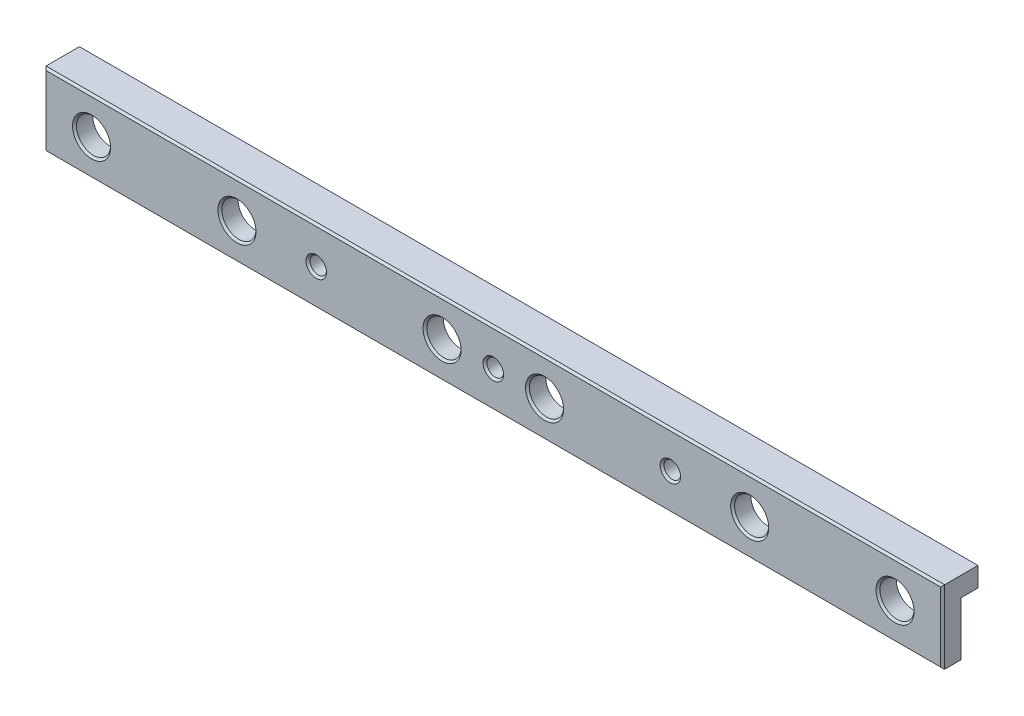
SolidWorks part; units mm, degrees
ref_plane "Front Plane" through (0, 0, 0) normal (0, 0, 1) x (1, 0, 0)
ref_plane "Top Plane" through (0, 0, 0) normal (0, 1, 0) x (1, 0, 0)
ref_plane "Right Plane" through (0, 0, 0) normal (1, 0, 0) x (0, 0, -1)
sketch "Sketch1" plane through (0, 0, 0) normal (0, 0, 1) x (1, 0, 0)
  line L0 (0, 7.5) -> (0, 0) construction
  line L1 (92, 7.5) -> (-92, 7.5)
  line L2 (92, 7.5) -> (92, 3.5)
  line L3 (92, -7.5) -> (-92, -7.5)
  line L4 (-92, 7.5) -> (-92, 3.5)
  line L5 (92, 3.5) -> (-92, 3.5)
  line L6 (-92, 3.5) -> (-92, -7.5)
  line L7 (92, 3.5) -> (92, -7.5)
  line L8 (0, 0) -> (0, -7.5) construction
  dimension "D1" = 92
  dimension "D2" = 7.5
  dimension "D3" = 4
extrude "Boss-Extrude1" add sketch "Sketch1" against normal blind 7.25 contours L7 L5 L6 L3 | L1 L0 L5 L2 | L0 L1 L4 L5 region at (46, 5.5, 0) region at (-46, 5.5, 0) region at (0, -2, 0)
extrude "Cut-Extrude1" cut sketch "Sketch1<6>" along normal blind 3.5 from surface contours L7 L5 L6 L3 region at (0, -2, 0) starting at face at (0, 0, -7.25)
sketch "Sketch1<6>" plane through (0, 0, 0) normal (0, 0, 1) x (1, 0, 0) same geometry as "Sketch1"
sketch "Sketch2" plane through (0, 0, 0) normal (0, 0, 1) x (1, 0, 0)
  line L0 (0, 7.5) -> (0, 0) construction
  circle A0 centre (-52.5, 0) radius 3.5
  circle A8 centre (-36.25, 0) radius 1.7
  circle A9 centre (-10.5, 0) radius 3.5
  circle A12 centre (0, 0) radius 1.7
  circle A13 centre (10.5, 0) radius 3.5
  circle A14 centre (36.25, 0) radius 1.7
  circle A15 centre (52.5, 0) radius 3.5
  circle A16 centre (-82.27, 0) radius 3.5
  circle A17 centre (82.27, 0) radius 3.5
  dimension "D2" = 7
  dimension "D4" = 29.77
  dimension "D3" = 7
  dimension "D1" = 3.4
extrude "Cut-Extrude2" cut sketch "Sketch2" against normal through all both and the other way through all
chamfer "Chamfer1" distance 0.4 angle 45 13 edges at (0, -7.5, 0) (-92, 0, 0) (0, 7.5, 0) (92, 0, 0) (56, 0, 0) (37.95, 0, 0) (14, 0, 0) (1.7, 0, 0) (-7, 0, 0) (-34.55, 0, 0) (-49, 0, 0) (-78.77, 0, 0) (85.77, 0, 0)
sketch "Sketch3" [suppressed] plane through (0, 0, 0) normal (0, 0, 1) x (1, 0, 0)
  line L0 (92, 7.5) -> (-92, 7.5) construction
  line L1 (92, 3.5) -> (-92, 3.5) construction
  line L3 (92, -7.5) -> (-92, -7.5) construction
  line L4 (0, 7.5) -> (0, 15) construction
  line L5 (7.5035, -7.5) -> (7.5035, -15) construction
  line L6 (0, 0) -> (0, -7.5) construction
  line L7 (7.6035, -7.5) -> (7.6035, -15)
  line L8 (0.1, 7.5) -> (0.1, 15)
  line L9 (7.4035, -7.5) -> (7.4035, -15)
  line L10 (-0.1, 7.5) -> (-0.1, 15)
  arc A0 (0, 7.5) -> (2.8723, 4.6277) centre (2.8723, 7.5) ccw construction
  arc A1 (2.1569, 2.6283) -> (2.8723, 4.6277) centre (2.8723, 3.5) ccw construction
  arc A2 (1.216, -3.1751) -> (7.5035, -7.5) centre (2.8723, -7.5) cw construction
  arc A3 (2.1569, 2.6283) -> (1.216, -3.1751) centre (0, 0) ccw construction
  arc A4 (1.1802, -3.0817) -> (7.6035, -7.5) centre (2.8723, -7.5) cw
  arc A5 (2.0935, 2.551) -> (1.1802, -3.0817) centre (0, 0) ccw
  arc A6 (2.0935, 2.551) -> (2.8723, 4.7277) centre (2.8723, 3.5) ccw
  arc A7 (0.1, 7.5) -> (2.8723, 4.7277) centre (2.8723, 7.5) ccw
  arc A8 (1.2517, -3.2685) -> (7.4035, -7.5) centre (2.8723, -7.5) cw
  arc A9 (2.2203, 2.7056) -> (1.2517, -3.2685) centre (0, 0) ccw
  arc A10 (2.2203, 2.7056) -> (2.8723, 4.5277) centre (2.8723, 3.5) ccw
  arc A11 (-0.1, 7.5) -> (2.8723, 4.5277) centre (2.8723, 7.5) ccw
  arc A12 (7.6035, -15) -> (7.4035, -15) centre (7.5035, -15) cw
  arc A13 (0.1, 15) -> (-0.1, 15) centre (0, 15) ccw
  dimension "D1" = 0.1
  dimension "D2" = 0.1
extrude "Cut-Extrude4" [suppressed] cut sketch "Sketch3" against normal through all both and the other way through all
